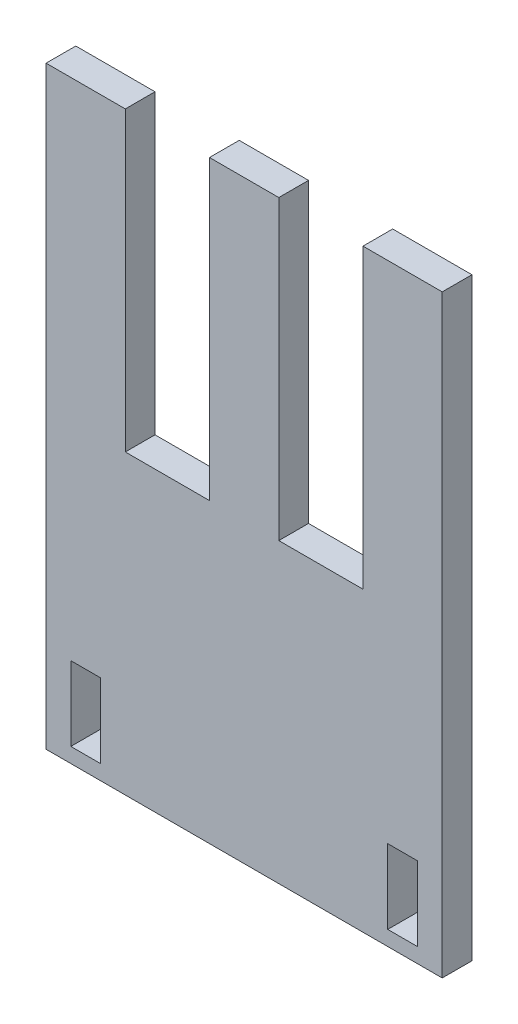
SolidWorks part; units mm, degrees
ref_plane "Plan de face" through (0, 0, 0) normal (0, 0, 1) x (1, 0, 0)
ref_plane "Plan de dessus" through (0, 0, 0) normal (0, 1, 0) x (1, 0, 0)
ref_plane "Plan de droite" through (0, 0, 0) normal (1, 0, 0) x (0, 0, -1)
sketch "Esquisse1" plane through (0, 0, 0) normal (0, 0, 1) x (1, 0, 0)
  line L0 (7.0676, 47.3813) -> (7.0676, -12.6187)
  line L1 (23.0676, 47.3813) -> (7.0676, 47.3813)
  line L2 (-56.9324, 47.3813) -> (-56.9324, -72.6187)
  line L3 (-56.9324, -72.6187) -> (23.0676, -72.6187)
  line L4 (23.0676, 47.3813) -> (23.0676, -72.6187)
  line L5 (18.0676, -54.6187) -> (12.0676, -54.6187)
  line L6 (18.0676, -54.6187) -> (18.0676, -69.6187)
  line L7 (18.0676, -69.6187) -> (12.0676, -69.6187)
  line L8 (12.0676, -54.6187) -> (12.0676, -69.6187)
  line L9 (-45.9324, -54.6187) -> (-51.9324, -54.6187)
  line L10 (-45.9324, -54.6187) -> (-45.9324, -69.6187)
  line L11 (-45.9324, -69.6187) -> (-51.9324, -69.6187)
  line L12 (-51.9324, -54.6187) -> (-51.9324, -69.6187)
  line L13 (7.0676, -12.6187) -> (-9.9324, -12.6187)
  line L14 (-9.9324, -12.6187) -> (-9.9324, 47.3813)
  line L15 (-9.9324, 47.3813) -> (-23.9324, 47.3813)
  line L16 (-23.9324, 47.3813) -> (-23.9324, -12.6187)
  line L17 (-23.9324, -12.6187) -> (-40.9324, -12.6187)
  line L18 (-40.9324, -12.6187) -> (-40.9324, 47.3813)
  line L19 (-40.9324, 47.3813) -> (-56.9324, 47.3813)
  dimension "D1" = 120
  dimension "D2" = 80
  dimension "D3" = 6
  dimension "D4" = 15
  dimension "D5" = 6
  dimension "D6" = 15
  dimension "D7" = 5
  dimension "D8" = 5
  dimension "D9" = 3
  dimension "D10" = 3
  dimension "D11" = 16
  dimension "D12" = 17
  dimension "D13" = 16
  dimension "D14" = 17
  dimension "D15" = 14
  dimension "D16" = 60
  dimension "D17" = 60
  dimension "D18" = 60
extrude "Boss.-Extru.1" add sketch "Esquisse1" along normal blind 6
